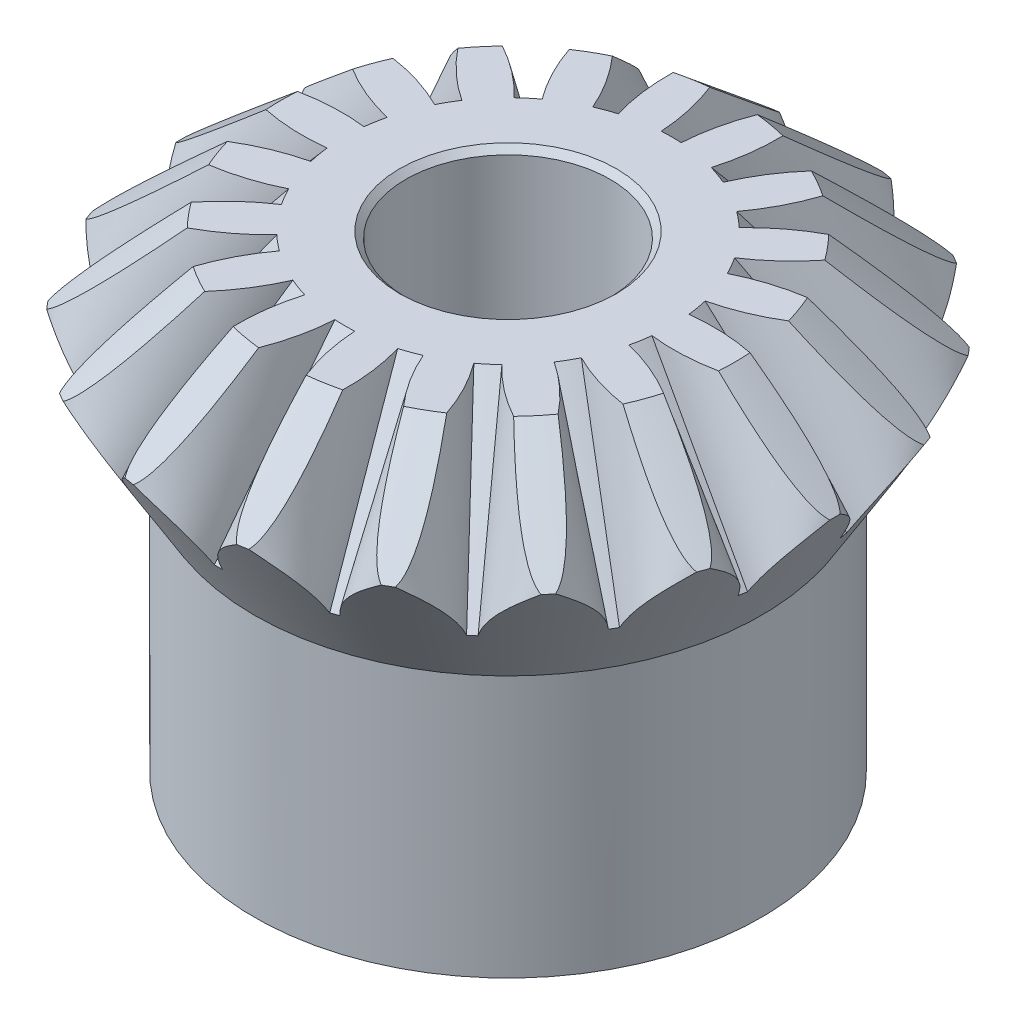
SolidWorks part; units mm, degrees
ref_plane "Front Plane" through (0, 0, 0) normal (0, 0, 1) x (1, 0, 0)
ref_plane "Top Plane" through (0, 0, 0) normal (0, 1, 0) x (1, 0, 0)
ref_plane "Right Plane" through (0, 0, 0) normal (1, 0, 0) x (0, 0, -1)
sketch "Sketch1" plane through (0, 0, 0) normal (1, 0, 0) x (0, 0, -1)
  line L0 (0, 3.6322) -> (0, -3.6322) construction
  line L1 (-3.937, -3.6322) -> (3.937, -3.6322) construction
  line L2 (3.937, -3.6322) -> (3.937, 0.4318) construction
  line L3 (-3.5234, 3.6322) -> (3.5234, 3.6322) construction
  line L4 (-5.08, 2.3261) -> (5.08, 2.3261) construction
  line L5 (5.08, 2.3261) -> (3.5234, 3.6322) construction
  line L7 (-3.5234, 3.6322) -> (-5.08, 2.3261) construction
  line L8 (0, 6.6802) -> (7.2644, 6.6802) construction
  point P0 (0, 6.6802)
  point P4 (0, 0)
  point P9 (0, -3.6322)
  point P12 (-1.5875, 3.6322)
  point P13 (1.5875, 3.6322)
  point P14 (0, 3.6322)
  point P15 (4.7625, 2.3261)
  point P18 (0, 2.3261)
  point P20 (-4.7625, 2.3261)
  dimension "Overall Width" = 7.2644
  dimension "Mounting Distance" = 10.3124
  dimension "Hub Diameter" = 7.874
  dimension "Hub Width" = 4.064
  dimension "Face Width" = 2.032
  dimension "For Shaft Diameter" = 3.175
  dimension "OD" = 10.16
  dimension "Gear Pitch Diameter" = 9.525
  dimension "For Shaft Angle" = 90
  dimension "D1" = 40
sketch "Sketch2" plane through (0, 0, 0) normal (0, 1, 0) x (1, 0, 0)
  circle A0 centre (0, 0) radius 5.08
  circle A1 centre (0, 0) radius 4.7625
  point P4 (0, -4.7625)
  point P7 (-1.6289, -4.4753)
  point P10 (-3.0613, -3.6483)
  point P11 (-4.1244, -2.3812)
  point P12 (-4.6901, -0.827)
  point P13 (-4.6901, 0.827)
  point P14 (-4.1244, 2.3813)
  point P15 (-3.0613, 3.6483)
  point P16 (-1.6289, 4.4753)
  point P17 (0, 4.7625)
  point P18 (1.6289, 4.4753)
  point P19 (3.0613, 3.6483)
  point P20 (4.1244, 2.3812)
  point P21 (4.6901, 0.827)
  point P22 (4.6901, -0.827)
  point P23 (4.1244, -2.3813)
  point P24 (3.0613, -3.6483)
  point P25 (1.6289, -4.4753)
  point P28 (0, 0)
  dimension "Number of Teeth" = 18
sketch "Sketch3" plane through (0, 0, 0) normal (1, 0, 0) x (0, 0, -1)
  line L0 (0, 3.6322) -> (-3.5234, 3.6322)
  line L1 (-3.5234, 3.6322) -> (-5.08, 2.3261)
  line L2 (-5.08, 2.3261) -> (-3.937, 0.4318)
  line L3 (-3.937, 0.4318) -> (-3.937, -3.6322)
  line L4 (-3.937, -3.6322) -> (0, -3.6322)
  line L5 (0, -3.6322) -> (0, 3.6322)
revolve "Revolve1" add sketch "Sketch3" angle 360 about L5
sketch "Sketch4" plane through (0, 3.6322, 0) normal (0, 1, 0) x (1, 0, 0)
  circle A0 centre (0, 0) radius 1.5875
extrude "Cut-Extrude1" cut sketch "Sketch4" against normal through all both and the other way through all
ref_plane "Plane1" through (0, 2.3261, 5.08) normal (0, -0.5166, 0.8562) x (1, 0, 0)
sketch "Sketch5" plane through (0, 3.6322, 0) normal (0, 1, 0) x (1, 0, 0)
  line L0 (0, 0) -> (-0.1546, -2.5353) construction
  line L1 (0, 0) -> (0.1546, -2.5353) construction
  line L2 (-3.3237, -5.517) -> (3.3237, -5.517)
  line L3 (0, -2.54) -> (0, 0) construction
  circle A0 centre (0, 0) radius 4.7625 construction
  circle A1 centre (0, 0) radius 4.7625 construction
  circle A2 centre (0, 0) radius 5.08 construction
  circle A3 centre (0, 0) radius 5.08 construction
  arc A5 (-0.1546, -2.5353) -> (0.1546, -2.5353) centre (0, 0) ccw
  arc A8 (0.1546, -2.5353) -> (3.3237, -5.517) centre (3.3237, -2.342) ccw
  arc A9 (-3.3237, -5.517) -> (-0.1546, -2.5353) centre (-3.3237, -2.342) ccw
  dimension "D1" = 3.175
  dimension "D2" = 6.98
  dimension "D3" = 2.54
sketch "Sketch6" plane through (0, 0, 0) normal (1, 0, 0) x (0, 0, -1)
  line L1 (-2.54, 3.6322) -> (-4.4971, 1.3601)
  line L2 (-2.5353, 3.6322) -> (-5.517, 3.6322) construction
  line L3 (-5.08, 2.3261) -> (-3.937, 0.4318) construction
  dimension "D1" = 49.26
sketch "Sketch7" plane through (0, 2.3261, 5.08) normal (0, -0.5166, 0.8562) x (1, 0, 0)
  line L0 (-1.7145, 0.0841) -> (1.7145, 0.0841) construction
  line L1 (0, -1.5062) -> (-0.0632, -1.1282) construction
  line L2 (0, -1.5062) -> (0.0632, -1.1282) construction
  line L3 (-0.0632, -1.1282) -> (0.0632, -1.1282)
  line L4 (-1.5119, 0.0981) -> (1.5119, 0.0981)
  arc A1 (-0.0632, -1.1282) -> (-1.5119, 0.0981) centre (-1.5119, -1.3707) ccw
  arc A2 (1.5119, 0.0981) -> (0.0632, -1.1282) centre (1.5119, -1.3707) ccw
  ellipse E1 centre (0, -2.6245) end of major axis (-4.5665, -2.6245) minor radius 2.9224 construction
  ellipse E2 centre (0, -1.5062) end of major axis (-3.5234, -1.5062) minor radius 1.8203 construction
  point P24 (0, 0.0981)
  dimension "D2" = 3.429
  dimension "D1" = 19
  dimension "D3" = 4.5665
loft "Cut-Loft1" cut profiles "Sketch5", "Sketch7"
pattern_circular "CirPattern2" count 18 over 360 about axis through (0, 3.6322, 0) along (0, -1, 0) of "Cut-Loft1"
chamfer "Chamfer1" distance 0.0953 angle 45 2 edges at (0, -3.6322, 1.5875) (0, 3.6322, -1.5875)
sketch "Sketch8" plane through (0, 0, 0) normal (1, 0, 0) x (0, 0, -1)
  line L1 (3.048, 6.6802) -> (3.048, 10.2036)
  line L9 (3.048, 6.6802) -> (3.048, 3.1568) construction
  line L10 (3.048, 10.2036) -> (4.3541, 11.9969)
  line L14 (3.048, 3.1568) -> (4.3541, 1.6002) construction
  line L15 (4.3541, 11.9969) -> (6.2484, 10.6172)
  line L16 (6.2484, 10.6172) -> (10.3124, 10.6172)
  line L17 (10.3124, 10.6172) -> (10.3124, 6.6802)
  line L18 (10.3124, 6.6802) -> (10.3124, 2.7432)
  line L19 (10.3124, 2.7432) -> (6.2484, 2.7432)
  line L20 (6.2484, 2.7432) -> (5.08, 2.3261)
  line L21 (4.3541, 1.6002) -> (6.2484, 2.7432) construction
  line L22 (6.2484, 2.7432) -> (10.3124, 2.7432) construction
  line L23 (10.3124, 2.7432) -> (10.3124, 6.6802) construction
  line L24 (10.3124, 6.6802) -> (3.048, 6.6802) construction
  line L25 (0, 3.6322) -> (-3.5234, 3.6322)
  line L26 (-3.5234, 3.6322) -> (-5.08, 2.3261)
  line L27 (-5.08, 2.3261) -> (-3.937, 0.4318)
  line L28 (-3.937, 0.4318) -> (-3.937, -3.6322)
  line L29 (-3.937, -3.6322) -> (0, -3.6322)
  line L30 (0, -3.6322) -> (0, 3.6322)
  line L31 (0, 3.6322) -> (-3.5234, 3.6322)
  line L32 (-3.5234, 3.6322) -> (-5.08, 2.3261)
  line L33 (-5.08, 2.3261) -> (-3.937, 0.4318)
  line L34 (-3.937, 0.4318) -> (-3.937, -3.6322)
  line L35 (-3.937, -3.6322) -> (0, -3.6322)
  line L36 (0, -3.6322) -> (0, 3.6322)
  line L37 (0, 6.6802) -> (7.2644, 6.6802) construction
  line L38 (5.08, 2.3261) -> (3.5234, 3.6322)
  line L39 (3.5234, 3.6322) -> (3.048, 3.6322)
  line L40 (3.048, 3.6322) -> (3.048, 6.6802)
  line L41 (1.778, 6.6802) -> (11.5824, 6.6802)
  line L42 (0, 4.9022) -> (0, -4.9022)
  point P15 (0, 6.6802)
  point P19 (3.937, -3.6322)
  point P20 (-3.937, -3.6322)
  point P21 (-3.937, 0.4318)
  point P22 (-3.5234, 3.6322)
  point P23 (-5.08, 2.3261)
  point P25 (10.3124, 10.6172)
  point P26 (0, 3.6322)
  dimension "D3" = 1.27
  dimension "D4" = 1.27
  dimension "D5" = 1.27
  dimension "D2" = 2
sketch "Sketch9" plane through (0, 0, 0) normal (0, 1, 0) x (1, 0, 0)
  circle A0 centre (0, 0) radius 5.08
  circle A1 centre (0, 0) radius 4.7625
  circle A2 centre (0, 0) radius 1.5875 construction
  circle A3 centre (0, 0) radius 1.5875
  point P6 (0, -5.08)
  point P7 (0, 5.08)
  point P8 (0, -4.7625)
  point P9 (0, 4.7625)
  point P10 (0, -1.5875)
  point P12 (0, 1.5875)
  point P17 (-1.5875, 0)
  point P18 (1.5875, 0)
  point P19 (-4.7625, 0)
  point P20 (-5.08, 0)
  point P21 (4.7625, 0)
  point P22 (5.08, 0)
equation "\"D1@CirPattern2\"=\"Number of Teeth@Sketch2\""
equation "\"D1@Chamfer1\"=\"For Shaft Diameter@Sketch1\"*.03"
equation "\"D4@Sketch8\"=\"D3@Sketch8\""
equation "\"D5@Sketch8\"=\"D3@Sketch8\""
